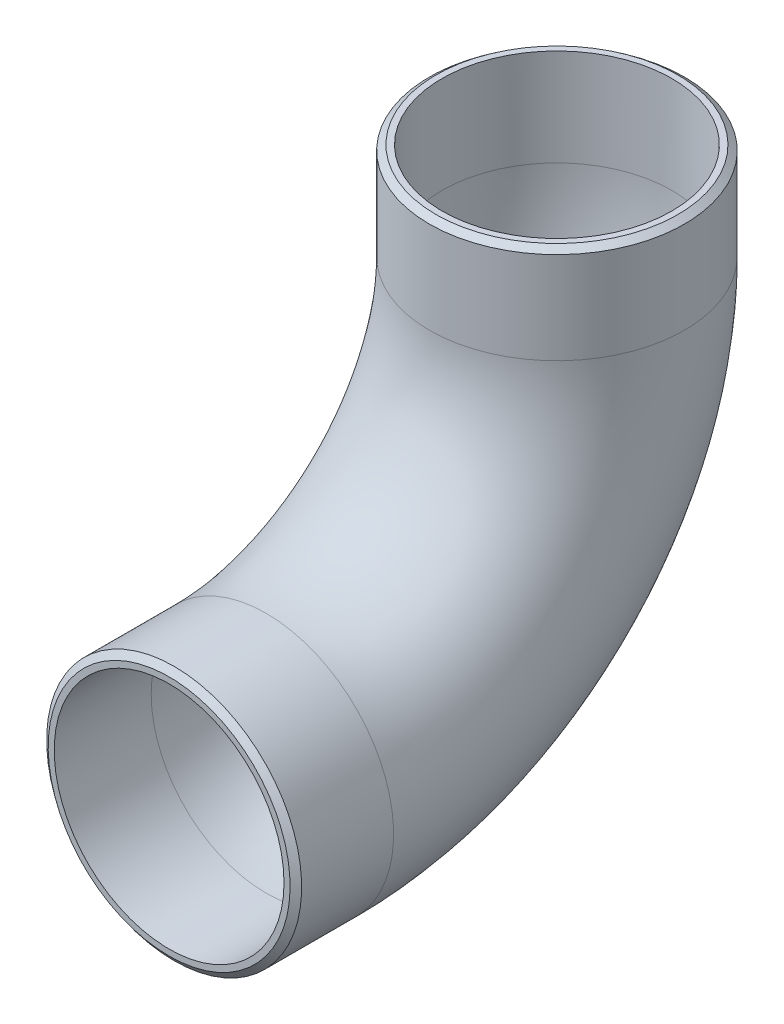
SolidWorks part; units mm, degrees
ref_plane "Front Plane" through (0, 0, 0) normal (0, 0, 1) x (1, 0, 0)
ref_plane "Top Plane" through (0, 0, 0) normal (0, 1, 0) x (1, 0, 0)
ref_plane "Right Plane" through (0, 0, 0) normal (1, 0, 0) x (0, 0, -1)
sketch "Sketch1" plane through (0, 0, 0) normal (1, 0, 0) x (0, 0, -1)
  line L0 (-50.8, 0) -> (-38.1, 0)
  line L1 (-38.1, 0) -> (0, 0) construction
  line L2 (0, 0) -> (0, 38.1) construction
  line L3 (0, 38.1) -> (0, 50.8)
  line L4 (-50.8, 15.0495) -> (-50.8, -15.0495) construction
  line L5 (-50.8, 15.0495) -> (-50.8, 16.7005) construction
  line L6 (-50.8, -15.0495) -> (-50.8, -16.7005) construction
  line L7 (-15.0495, 50.8) -> (15.0495, 50.8) construction
  line L8 (15.0495, 50.8) -> (16.7005, 50.8) construction
  line L9 (-15.0495, 50.8) -> (-16.7005, 50.8) construction
  line L12 (-38.1, 0) -> (-38.1, 38.1) construction
  line L13 (-38.1, 38.1) -> (0, 38.1) construction
  arc A0 (-38.1, 0) -> (0, 38.1) centre (-38.1, 38.1) ccw
  dimension "A" = 50.8
  dimension "OD" = 33.401
  dimension "Tanget" = 12.7
  dimension "WT" = 1.651
ref_plane "Plane1" through (0, 0, 50.8) normal (0, 0, 1) x (1, 0, 0)
sketch "Sketch2" plane through (0, 0, 50.8) normal (0, 0, 1) x (1, 0, 0)
  circle A0 centre (0, 0) radius 15.0495
  circle A1 centre (0, 0) radius 16.7005
sweep "Sweep1" add profiles "Sketch2" path "Sketch1"
sketch "Sketch3" plane through (0, 0, 0) normal (-1, 0, 0) x (0, 1, 0)
  line L0 (0, -50.8) -> (0, -38.1) construction
  line L1 (-16.7005, -50.8) -> (16.7005, -50.8) construction
  line L2 (16.7005, -38.1) -> (-16.7005, -38.1) construction
  line L3 (-16.7005, -50.8) -> (-16.7005, -50.1422)
  line L4 (-16.7005, -38.1) -> (-16.7005, -50.8) construction
  line L5 (-16.7005, -50.1422) -> (-15.8432, -50.8)
  line L6 (-15.8432, -50.8) -> (-16.7005, -50.8)
  line L7 (50.8, -15.0495) -> (50.8, 15.0495) construction
  line L8 (50.8, 0) -> (38.1, 0) construction
  line L9 (50.8, 15.8433) -> (50.8, 16.7005)
  line L10 (50.8, 16.7005) -> (50.1422, 16.7005)
  line L11 (50.8, 16.7005) -> (38.1, 16.7005) construction
  line L12 (50.1422, 16.7005) -> (50.8, 15.8433)
  line L13 (38.1, -16.7005) -> (38.1, 16.7005) construction
  point P11 (-15.0495, -50.8)
  dimension "T" = 0.7937
  dimension "A" = 37.5
revolve "Cut-Revolve1" cut sketch "Sketch3" angle 360 about L0
revolve "Cut-Revolve2" cut sketch "Sketch3<4>" angle 360 about L8
sketch "Sketch3<4>" plane through (0, 0, 0) normal (-1, 0, 0) x (0, 1, 0) same geometry as "Sketch3"
scale "Scale1" scale about centroid uniform scaling yes scale factor 0.095238
